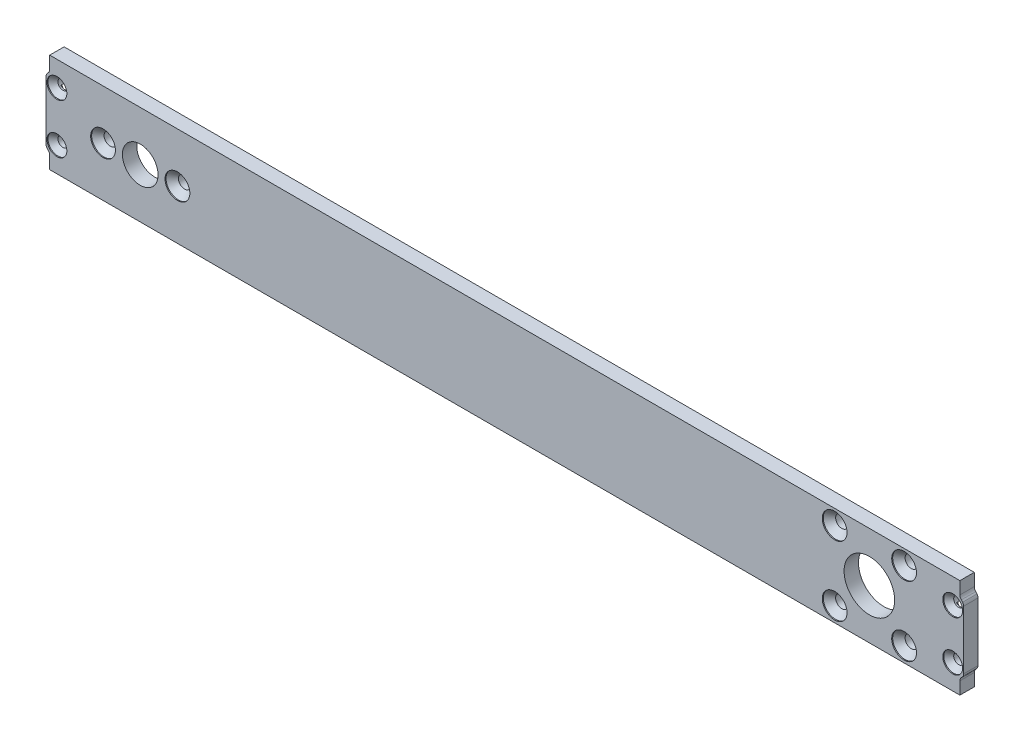
SolidWorks part; units mm, degrees
ref_plane "Front Plane" through (0, 0, 0) normal (0, 0, 1) x (1, 0, 0)
ref_plane "Top Plane" through (0, 0, 0) normal (0, 1, 0) x (1, 0, 0)
ref_plane "Right Plane" through (0, 0, 0) normal (1, 0, 0) x (0, 0, -1)
sketch "Sketch1" plane through (0, 0, 0) normal (0, 0, 1) x (1, 0, 0)
  line L1 (-92.5, 10) -> (92.5, 10)
  line L2 (-92.5, 10) -> (-92.5, -10)
  line L3 (-92.5, -10) -> (92.5, -10)
  line L4 (92.5, 10) -> (92.5, -10)
  line L5 (-92.5, 10) -> (92.5, -10) construction
  line L6 (-92.5, -10) -> (92.5, 10) construction
  point P0 (0, 0)
  dimension "D1" = 20
  dimension "D2" = 185
extrude "Base shape" add sketch "Sketch1" against normal blind 2.9
sketch "Sketch2" plane through (0, 0, 0) normal (0, 0, 1) x (1, 0, 0)
  line L0 (-83.5, 10) -> (-83.5, -10) construction
  line L1 (92.5, 10) -> (-92.5, 10) construction
  line L2 (-92.5, -10) -> (92.5, -10) construction
  line L3 (-92.5, 10) -> (-92.5, -10) construction
  line L4 (-92.5, 0) -> (92.5, 0) construction
  line L5 (92.5, -10) -> (92.5, 10) construction
  line L6 (-73.5, 10) -> (-73.5, -10) construction
  line L7 (0, 10) -> (0, -10) construction
  line L8 (73.5, 5.1) -> (92.5, 5.1) construction
  line L9 (-73.5, 3.6) -> (-92.5, 3.6) construction
  line L11 (80.5, -7) -> (66.5, -7)
  line L12 (80.5, -7) -> (80.5, 7)
  line L13 (80.5, 7) -> (66.5, 7)
  line L14 (66.5, -7) -> (66.5, 7)
  line L15 (80.5, -7) -> (66.5, 7) construction
  line L16 (80.5, 7) -> (66.5, -7) construction
  circle A0 centre (-73.5, 0) radius 10
  circle A1 centre (-81, 0) radius 1.25
  circle A2 centre (-66, 0) radius 1.25
  circle A3 centre (-73.5, 0) radius 3.6
  circle A4 centre (73.5, 0) radius 5.1
  circle A5 centre (66.5, 7) radius 1.25
  circle A6 centre (80.5, 7) radius 1.25
  circle A7 centre (80.5, -7) radius 1.25
  circle A8 centre (66.5, -7) radius 1.25
  dimension "D2" = 20
  dimension "D3" = 2.5
  dimension "D4" = 15
  dimension "D5" = 7.2
  dimension "D6" = 10.2
  dimension "D8" = 2.5
  dimension "D1" = 147
  dimension "D7" = 14
extrude "Motor cutouts" cut sketch "Sketch2" against normal up to next contours A5 | A6 | A7 | A8 | A1 | A2 | A3 | A4
sketch "Sketch5" plane through (0, 0, -2.9) normal (0, 0, -1) x (-1, 0, 0)
  line L0 (0, 10) -> (0, -10) construction
  line L3 (-92.5, 10) -> (92.5, 10) construction
  line L4 (92.5, -10) -> (-92.5, -10) construction
  line L5 (-60, -7) -> (60, -7) construction
  line L6 (-60, -6) -> (60, -6)
  line L7 (-60, -8) -> (60, -8)
  arc A0 (-60, -6) -> (-60, -8) centre (-60, -7) ccw
  arc A1 (60, -8) -> (60, -6) centre (60, -7) ccw
  point P8 (0, -7)
  dimension "D1" = 120
  dimension "D2" = 2
  dimension "D3" = 2
extrude "PCB slot" cut sketch "Sketch5" against normal blind 0.775
sketch "Sketch6" plane through (0, 0, 0) normal (0, 0, 1) x (1, 0, 0)
  line L0 (90.3, 10) -> (90.3, -10) construction
  line L1 (92.5, 10) -> (-92.5, 10) construction
  line L2 (-92.5, -10) -> (92.5, -10) construction
  line L3 (92.5, -10) -> (92.5, 10) construction
  line L4 (92.5, 0) -> (-92.5, 0) construction
  line L5 (-92.5, 10) -> (-92.5, -10) construction
  line L6 (0, 10) -> (0, -10) construction
  circle A0 centre (90.3, 5) radius 1
  circle A2 centre (90.3, -5) radius 1
  circle A3 centre (-90.3, -5) radius 1
  circle A5 centre (-90.3, 5) radius 1
  dimension "D2" = 2
  dimension "D1" = 2.2
  dimension "D3" = 10
extrude "End plate holes" cut sketch "Sketch6" against normal up to next
hole_wizard "Motor M2.5 countersunks" positions "Sketch3" profile "Sketch4" countersink size "M2.5" standard "ANSI Metric" end condition through all
sketch "Sketch3" plane through (0, 0, 0) normal (0, 0, 1) x (1, 0, 0)
  point P0 (-81, 0)
  point P3 (-66, 0)
  point P7 (66.5, 7)
  point P10 (80.5, 7)
  point P13 (66.5, -7)
  point P16 (80.5, -7)
sketch "Sketch4" plane through (-81, 0, 0) normal (1, 0, 0) x (0, -1, 0)
  line L0 (0, 0) -> (0, 2.9)
  line L1 (0, 2.9) -> (1.25, 2.9)
  line L2 (1.25, 2.9) -> (1.25, 1.45)
  line L3 (1.25, 1.45) -> (2.5, 0.2)
  line L4 (2.5, 0.2) -> (2.5, 0)
  line L6 (2.5, 0) -> (0, 0)
  line L7 (-1.25, 1.45) -> (-2.5, 0.2) construction
  line L11 (0, -6.35) -> (0, 107.95) construction
  dimension "Thru Hole Dia." = 2.5
  dimension "Thru Hole Depth" = 2.9
  dimension "C'Sink Dia." = 5
  dimension "C'Sink Angle" = 90
  dimension "Head Clearance" = 0.2
hole_wizard "End M2 countersunks" positions "Sketch10" profile "Sketch9" countersink size "M2" standard "ANSI Metric" end condition through all
sketch "Sketch10" plane through (0, 0, 0) normal (0, 0, 1) x (1, 0, 0)
  point P2 (90.3, 5)
  point P8 (90.3, -5)
  point P11 (-90.3, 5)
  point P17 (-90.3, -5)
sketch "Sketch9" plane through (90.3, 5, 0) normal (1, 0, 0) x (0, -1, 0)
  line L0 (0, 0) -> (0, 2.9)
  line L1 (0, 2.9) -> (1, 2.9)
  line L2 (1, 2.9) -> (1, 1.2)
  line L3 (1, 1.2) -> (2, 0.2)
  line L4 (2, 0.2) -> (2, 0)
  line L6 (2, 0) -> (0, 0)
  line L7 (-1, 1.2) -> (-2, 0.2) construction
  line L11 (0, -6.35) -> (0, 107.95) construction
  dimension "Thru Hole Dia." = 2
  dimension "Thru Hole Depth" = 2.9
  dimension "C'Sink Dia." = 4
  dimension "C'Sink Angle" = 90
  dimension "Head Clearance" = 0.2
sketch "Sketch12" plane through (0, 0, -2.9) normal (0, 0, -1) x (-1, 0, 0)
  line L0 (-92.5, 0) -> (92.5, 0) construction
  line L1 (-92.5, -10) -> (-92.5, 10) construction
  line L2 (92.5, 10) -> (92.5, -10) construction
  line L3 (-90.3, 5) -> (-90.3, -5) construction
  line L4 (-88.7, 4.05) -> (-91.9, 0.85) construction
  line L5 (-91.9, 4.05) -> (-88.7, 4.05)
  line L6 (-91.9, 4.05) -> (-91.9, -4.05)
  line L7 (-91.9, -4.05) -> (-88.7, -4.05)
  line L8 (-88.7, 4.05) -> (-88.7, -4.05)
  line L9 (-91.9, 4.05) -> (-88.7, -4.05) construction
  line L10 (-91.9, -4.05) -> (-88.7, 4.05) construction
  line L11 (0, 10) -> (0, -10) construction
  line L12 (-92.5, 10) -> (92.5, 10) construction
  line L13 (92.5, -10) -> (-92.5, -10) construction
  line L14 (91.9, -4.05) -> (88.7, -4.05)
  line L15 (91.9, 4.05) -> (88.7, 4.05)
  line L16 (91.9, 4.05) -> (91.9, -4.05)
  line L17 (88.7, 4.05) -> (88.7, -4.05)
  line L18 (-91.1929, 4.3429) -> (-89.4071, 4.3429)
  line L19 (-91.1929, -4.3429) -> (-89.4071, -4.3429)
  line L20 (91.1929, 4.3429) -> (89.4071, 4.3429)
  line L21 (91.1929, -4.3429) -> (89.4071, -4.3429)
  circle A0 centre (-89.4071, 3.3429) radius 1
  circle A1 centre (-91.1929, 3.3429) radius 1
  circle A2 centre (-89.4071, -3.3429) radius 1
  circle A3 centre (-91.1929, -3.3429) radius 1
  circle A4 centre (89.4071, -3.3429) radius 1
  circle A5 centre (91.1929, -3.3429) radius 1
  circle A6 centre (89.4071, 3.3429) radius 1
  circle A7 centre (91.1929, 3.3429) radius 1
  point P10 (-90.3, 0)
  circle M9 centre (-90.3, -5) radius 1
  circle M10 centre (90.3, -5) radius 1
  circle M11 centre (90.3, 5) radius 1
  circle M12 centre (-90.3, 5) radius 1
  dimension "D3" = 2
  dimension "D1" = 3.2
  dimension "D2" = 8.1
  dimension "D4" = 45
extrude "Tap slots" cut sketch "Sketch12" against normal blind 1.4 contours A1 L5 A0 L18 M12 | A3 L19 A2 L7 M9 | A7 L20 A6 L15 M11 | A5 L14 A4 L21 M10 | A1 | A0 | A2 | A3 | L6 L7 L8 L5 | A6 | A7 | A5 | A4 | L17 L14 L16 L15 region at (90.3, 4.2292, -2.9) region at (90.3, -4.2292, -2.9) region at (-90.3, -4.2292, -2.9) region at (-90.3, 4.2292, -2.9)
sketch "Sketch13" plane through (0, 0, 0) normal (0, 0, 1) x (1, 0, 0)
  line L0 (-92.5, -10) -> (92.5, -10) construction
  line L1 (-92.5, 10) -> (-91.75, 10)
  line L2 (-92.5, 10) -> (-92.5, -10)
  line L3 (-92.5, -10) -> (-91.75, -10)
  line L4 (-91.75, 10) -> (-91.75, -10)
  line L5 (-92.5, 0) -> (92.5, 0) construction
  line L6 (92.5, -10) -> (92.5, 10) construction
  line L7 (0, 10) -> (0, -10) construction
  line L8 (92.5, 10) -> (-92.5, 10) construction
  line L9 (92.5, -10) -> (91.75, -10)
  line L10 (91.75, 10) -> (91.75, -10)
  line L11 (92.5, 10) -> (91.75, 10)
  line L12 (92.5, 10) -> (92.5, -10)
  circle A0 centre (-90.3, 5) radius 2.5
  circle A1 centre (-90.3, -5) radius 2.5
  circle A2 centre (90.3, 5) radius 2.5
  circle A3 centre (90.3, -5) radius 2.5
  line M16 (92.5, -10) -> (92.5, 10)
  line M17 (92.5, 10) -> (-92.5, 10)
  line M18 (-92.5, 10) -> (-92.5, -10)
  line M19 (-92.5, -10) -> (92.5, -10)
  dimension "D2" = 5
  dimension "D1" = 0.75
extrude "Cut-Extrude3" cut sketch "Sketch13" against normal up to next contours A0 L4 M17 M18 | A1 L4 M18 M19 | L10 A2 M16 M17 | A3 L10 M16 M19 region at (-92.1406, 8.3301, 0) region at (92.1406, 8.3301, 0) region at (-92.1406, -8.3301, 0) region at (92.1406, -8.3301, 0)
fillet "Fillet1" radius 1 8 edges at (-91.75, -7.0365, -1.45) (-92.5, -6.1874, -1.45) (-92.5, 6.1874, -1.45) (-91.75, 7.0365, -1.45) (92.5, 6.1874, -1.45) (91.75, 7.0365, -1.45) (92.5, -6.1874, -1.45) (91.75, -7.0365, -1.45)
